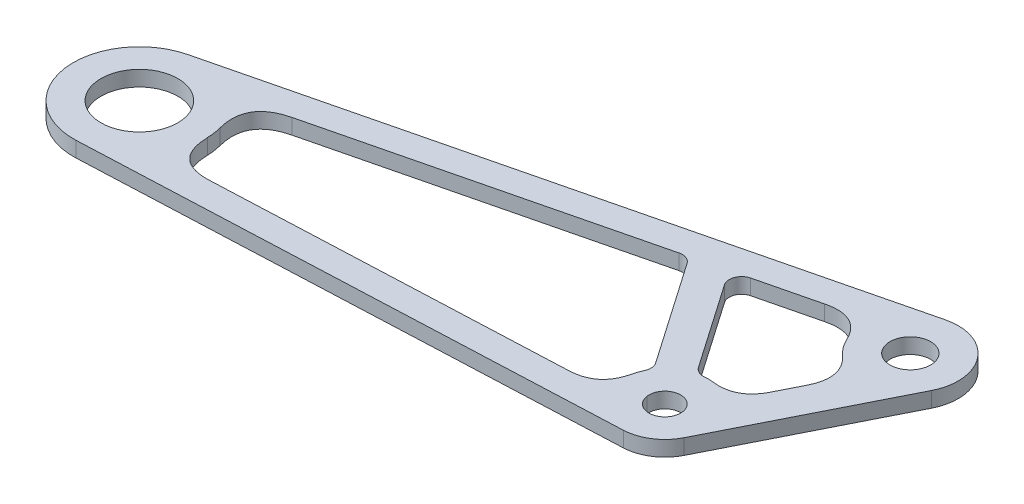
SolidWorks part; units mm, degrees
material "6061-T6 (SS)"
ref_plane "Front Plane" through (0, 0, 0) normal (0, 0, 1) x (1, 0, 0)
ref_plane "Top Plane" through (0, 0, 0) normal (0, 1, 0) x (1, 0, 0)
ref_plane "Right Plane" through (0, 0, 0) normal (1, 0, 0) x (0, 0, -1)
sketch "Sketch1" plane through (0, 0, 0) normal (0, 1, 0) x (1, 0, 0)
  line L0 (0, 0) -> (124.8778, 34.4406) construction
  line L1 (124.8778, 34.4406) -> (108.585, 0) construction
  line L2 (108.585, 0) -> (0, 0) construction
  line L3 (-3.2476, 13.2606) -> (122.5214, 44.0623)
  line L5 (116.6057, -4.036) -> (133.7266, 29.9879)
  line L6 (108.585, 0) -> (109.8191, -8.8937) construction
  line L7 (-1.8881, 7.7097) -> (123.8808, 38.5113)
  line L8 (111.5006, -1.4671) -> (128.6215, 32.5568)
  line L9 (0.3416, -7.9301) -> (108.7255, -3.2609)
  line L10 (108.585, 0) -> (88.0141, 29.7273) construction
  line L11 (108.585, 0) -> (108.585, 29.9472) construction
  line L12 (60.9963, 23.1105) -> (39.4816, -6.244) construction
  line L13 (65.794, 24.2855) -> (43.5464, -6.0688)
  line L14 (56.1987, 21.9355) -> (35.4168, -6.4191)
  line L15 (84.7126, 28.9188) -> (101.195, 5.0998)
  line L16 (91.3157, 30.5359) -> (106.4167, 8.7132)
  line L17 (50.239, 8.4333) -> (47.6782, 10.3102) construction
  line L18 (50.239, 8.4333) -> (52.7998, 6.5564) construction
  line L19 (98.2996, 14.8637) -> (95.6887, 13.057) construction
  line L20 (98.2996, 14.8637) -> (100.9104, 16.6703) construction
  line L21 (114.3014, 6.9241) -> (123.2323, 24.6722)
  line L22 (0.5876, -13.6398) -> (108.9715, -8.9706)
  circle A0 centre (0, 0) radius 7.9375
  circle A1 centre (124.8778, 34.4406) radius 4.191
  circle A2 centre (108.585, 0) radius 3.2639
  circle A3 centre (0, 0) radius 13.6525
  circle A4 centre (108.585, 0) radius 8.9789
  circle A5 centre (124.8778, 34.4406) radius 9.906
  arc A6 (-3.2476, 13.2606) -> (6.5337, -11.9876) centre (0, 0) ccw
  arc A7 (116.6057, -4.036) -> (108.585, -8.9789) centre (108.585, 0) cw
  arc A8 (122.5214, 44.0623) -> (133.7266, 29.9879) centre (124.8778, 34.4406) cw
  point P44 (0, 0)
  point P45 (0, 0)
  point P48 (0, 0)
  dimension "D4" = 15.875
  dimension "D5" = 6.5278
  dimension "D6" = 8.382
  dimension "D7" = 5.715
  dimension "D8" = 5.715
  dimension "D9" = 5.715
  dimension "D1" = 129.54
  dimension "D2" = 38.1
  dimension "D3" = 108.585
  dimension "D10" = 97.9
  dimension "D11" = 60
  dimension "D12" = 40
  dimension "D13" = 6.35
  dimension "D14" = 1.27
extrude "Boss-Extrude4" add sketch "Sketch1" against normal blind 3.175 contours A3 L9 A0 L7 | L9 A3 L7 A0 | A5 L3 A3 L7 | A4 L9 A3 L22 | A4 L16 L7 L15 | A4 L8 A2 L9 | L8 A4 L9 A2 | A5 L8 A4 L5 | L8 A5 L7 A1 | L7 A5 L8 A1 | A5 L21 A4 L8 region at (3.0925, 0, -12.9166) region at (60.9421, 0, -26.1046) region at (130.8206, 0, -42.0146) region at (55.5019, 0, 8.4889) region at (9.0069, 0, -1.2841) region at (120.3421, 0, -30.8296) region at (110.8898, 0, 3.5657) region at (122.752, 0, -13.9922) region at (95.7558, 0, -18.4572) region at (119.3495, 0, -15.5333) region at (106.4195, 0, -3.3502)
ref_plane "Plane1" through (108.585, 0, 0) normal (0.1374, 0, 0.9905) x (0.9905, 0, -0.1374)
split line "Split Line1"
sketch "Sketch2" [suppressed] plane through (0, -3.175, 0) normal (0, -1, 0) x (1, 0, 0)
  line L1 (69.4473, -23.6659) -> (60.7288, -1.2641)
  line L2 (62.8949, 2.1892) -> (101.6127, 5.2609)
  line L3 (101.2476, -37.8411) -> (79.7056, -31.0891)
  line L4 (79.2148, -26.4545) -> (98.3531, -15.6299)
  line L5 (59.9072, -25.992) -> (7.538, -8.592)
  line L6 (63.0965, -22.7173) -> (54.4829, 1.0899)
  line L7 (51.7805, 2.7463) -> (11.1946, -2.3078)
  line L8 (73.1912, -24.8791) -> (102.155, -6.1958)
  line L9 (104.5239, -35.0732) -> (102.1201, -17.4966)
  circle A0 centre (111.76, 0) radius 11.43 construction
  circle A3 centre (0, 0) radius 11.43 construction
  arc A4 (11.1946, -2.3078) -> (7.538, -8.592) centre (0, 0) cw
  arc A5 (101.6127, 5.2609) -> (102.155, -6.1958) centre (111.76, 0) ccw
  arc A6 (101.2476, -37.8411) -> (104.5239, -35.0732) centre (102.0073, -35.4173) ccw
  arc A7 (98.3531, -15.6299) -> (102.1201, -17.4966) centre (99.6035, -17.8407) cw
  arc A8 (69.4473, -23.6659) -> (73.1912, -24.8791) centre (71.8144, -22.7446) ccw
  arc A9 (60.7288, -1.2641) -> (62.8949, 2.1892) centre (63.0958, -0.3428) cw
  arc A10 (63.0965, -22.7173) -> (59.9072, -25.992) centre (60.7081, -23.5815) cw
  arc A11 (54.4829, 1.0899) -> (51.7805, 2.7463) centre (52.0944, 0.2257) ccw
  arc A12 (79.2148, -26.4545) -> (79.7056, -31.0891) centre (80.4653, -28.6654) ccw
  dimension "D1" = 2.54
  dimension "D2" = 2.54
  dimension "D3" = 2.54
  dimension "D4" = 2.54
  dimension "D5" = 2.54
  dimension "D6" = 2.54
  dimension "D7" = 2.54
extrude "Cut-Extrude2" [suppressed] cut sketch "Sketch2" against normal through all
fillet "Fillet1" radius 7.62 6 edges at (115.1627, -1.5875, -36.3762) (8.901, -1.5875, -10.352) (114.3014, -1.5875, -6.9241) (123.2323, -1.5875, -24.6722) (11.4393, -1.5875, 7.452) (100.3686, -1.5875, 3.6209) conic rho 0.5
fillet "Fillet2" radius 2.54 4 edges at (91.3157, -1.5875, -30.5359) (106.4167, -1.5875, -8.7132) (101.195, -1.5875, -5.0998) (84.7126, -1.5875, -28.9188)
equation "\"x\"= .05"
